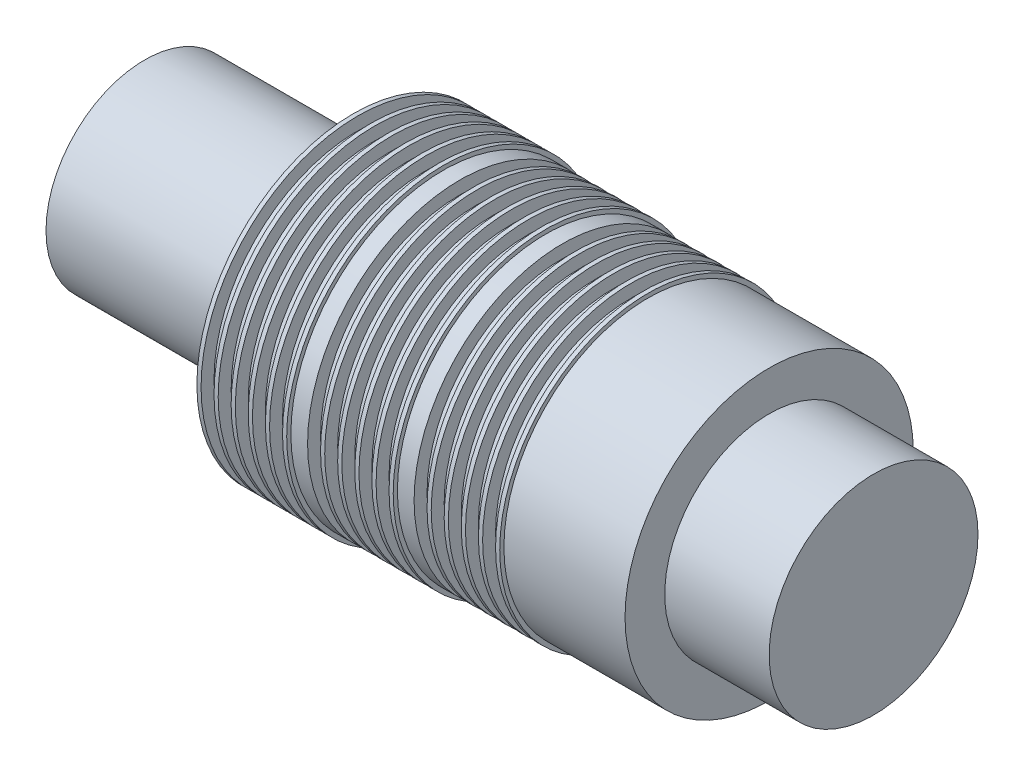
SolidWorks part; units mm, degrees
ref_plane "Front Plane" through (0, 0, 0) normal (0, 0, 1) x (1, 0, 0)
ref_plane "Top Plane" through (0, 0, 0) normal (0, 1, 0) x (1, 0, 0)
ref_plane "Right Plane" through (0, 0, 0) normal (1, 0, 0) x (0, 0, -1)
sketch "Sketch1" plane through (0, 0, 0) normal (0, 0, 1) x (1, 0, 0)
  line L24 (12.954, 9.525) -> (12.954, 8.7376)
  line L25 (12.954, 8.7376) -> (13.7414, 8.7376)
  line L26 (13.7414, 8.7376) -> (13.7414, 9.525)
  line L27 (13.7414, 9.525) -> (13.9954, 9.525)
  line L28 (13.9954, 9.525) -> (13.9954, 8.7376)
  line L29 (13.9954, 8.7376) -> (14.7828, 8.7376)
  line L30 (14.7828, 8.7376) -> (14.7828, 9.525)
  line L31 (14.7828, 9.525) -> (15.0368, 9.525)
  line L32 (15.0368, 9.525) -> (15.0368, 8.7376)
  line L33 (15.0368, 8.7376) -> (15.8242, 8.7376)
  line L34 (15.8242, 8.7376) -> (15.8242, 9.525)
  line L35 (15.8242, 9.525) -> (16.0782, 9.525)
  line L36 (16.0782, 9.525) -> (16.0782, 8.7376)
  line L37 (16.0782, 8.7376) -> (16.8656, 8.7376)
  line L38 (16.8656, 8.7376) -> (16.8656, 9.525)
  line L39 (16.8656, 9.525) -> (17.1196, 9.525)
  line L40 (17.1196, 9.525) -> (17.1196, 8.7376)
  line L41 (17.1196, 8.7376) -> (17.907, 8.7376)
  line L42 (17.907, 8.7376) -> (17.907, 9.525)
  line L43 (17.907, 9.525) -> (18.161, 9.525)
  line L44 (18.161, 9.525) -> (18.161, 9.271)
  line L45 (18.161, 9.271) -> (19.177, 9.271)
  line L46 (19.177, 9.271) -> (19.177, 8.4836)
  line L47 (19.177, 8.4836) -> (19.9644, 8.4836)
  line L48 (19.9644, 8.4836) -> (19.9644, 9.271)
  line L49 (19.9644, 9.271) -> (20.2184, 9.271)
  line L50 (20.2184, 9.271) -> (20.2184, 8.4836)
  line L51 (20.2184, 8.4836) -> (21.0058, 8.4836)
  line L52 (21.0058, 8.4836) -> (21.0058, 9.271)
  line L53 (21.0058, 9.271) -> (21.2598, 9.271)
  line L54 (21.2598, 9.271) -> (21.2598, 8.4836)
  line L55 (21.2598, 8.4836) -> (22.0472, 8.4836)
  line L56 (22.0472, 8.4836) -> (22.0472, 9.271)
  line L57 (22.0472, 9.271) -> (22.3012, 9.271)
  line L58 (22.3012, 9.271) -> (22.3012, 8.4836)
  line L59 (22.3012, 8.4836) -> (23.0886, 8.4836)
  line L60 (23.0886, 8.4836) -> (23.0886, 9.271)
  line L61 (23.0886, 9.271) -> (23.3426, 9.271)
  line L62 (23.3426, 9.271) -> (23.3426, 8.4836)
  line L63 (23.3426, 8.4836) -> (24.13, 8.4836)
  line L64 (24.13, 8.4836) -> (24.13, 9.271)
  line L65 (24.13, 9.271) -> (24.384, 9.271)
  line L66 (24.384, 9.271) -> (24.384, 9.017)
  line L67 (24.384, 9.017) -> (25.4, 9.017)
  line L68 (25.4, 9.017) -> (25.4, 8.2296)
  line L69 (25.4, 8.2296) -> (26.1874, 8.2296)
  line L70 (26.1874, 8.2296) -> (26.1874, 9.017)
  line L71 (26.1874, 9.017) -> (26.4414, 9.017)
  line L72 (26.4414, 9.017) -> (26.4414, 8.2296)
  line L73 (26.4414, 8.2296) -> (27.2288, 8.2296)
  line L74 (27.2288, 8.2296) -> (27.2288, 9.017)
  line L75 (27.2288, 9.017) -> (27.4828, 9.017)
  line L76 (27.4828, 9.017) -> (27.4828, 8.2296)
  line L77 (27.4828, 8.2296) -> (28.2702, 8.2296)
  line L78 (28.2702, 8.2296) -> (28.2702, 9.017)
  line L79 (28.2702, 9.017) -> (28.5242, 9.017)
  line L80 (28.5242, 9.017) -> (28.5242, 8.2296)
  line L81 (28.5242, 8.2296) -> (29.3116, 8.2296)
  line L82 (29.3116, 8.2296) -> (29.3116, 9.017)
  line L83 (29.3116, 9.017) -> (29.5656, 9.017)
  line L84 (29.5656, 9.017) -> (29.5656, 8.2296)
  line L85 (29.5656, 8.2296) -> (30.353, 8.2296)
  line L86 (30.353, 8.2296) -> (30.353, 9.017)
  line L87 (30.353, 9.017) -> (30.607, 9.017)
  line L88 (30.607, 9.017) -> (30.607, 8.763)
  line L89 (30.607, 8.763) -> (31.623, 8.763)
  line L90 (31.623, 8.763) -> (31.623, 7.9756)
  line L91 (31.623, 7.9756) -> (32.4104, 7.9756)
  line L92 (32.4104, 7.9756) -> (32.4104, 8.763)
  line L93 (32.4104, 8.763) -> (32.6644, 8.763)
  line L94 (32.6644, 8.763) -> (32.6644, 7.9756)
  line L95 (32.6644, 7.9756) -> (33.4518, 7.9756)
  line L96 (33.4518, 7.9756) -> (33.4518, 8.763)
  line L97 (33.4518, 8.763) -> (33.7058, 8.763)
  line L98 (33.7058, 8.763) -> (33.7058, 7.9756)
  line L99 (33.7058, 7.9756) -> (34.4932, 7.9756)
  line L100 (34.4932, 7.9756) -> (34.4932, 8.763)
  line L101 (34.4932, 8.763) -> (34.7472, 8.763)
  line L102 (34.7472, 8.763) -> (34.7472, 7.9756)
  line L103 (34.7472, 7.9756) -> (35.5346, 7.9756)
  line L104 (35.5346, 7.9756) -> (35.5346, 8.763)
  line L105 (35.5346, 8.763) -> (35.7886, 8.763)
  line L106 (35.7886, 8.763) -> (35.7886, 7.9756)
  line L107 (35.7886, 7.9756) -> (36.576, 7.9756)
  line L108 (36.576, 7.9756) -> (36.576, 8.763)
  line L109 (36.576, 8.763) -> (36.83, 8.763)
  line L110 (36.83, 8.763) -> (36.83, 8.509)
  line L111 (36.83, 8.509) -> (37.846, 8.509)
  line L112 (37.846, 8.509) -> (37.846, 7.7216)
  line L113 (37.846, 7.7216) -> (38.6334, 7.7216)
  line L114 (38.6334, 7.7216) -> (38.6334, 8.509)
  line L115 (38.6334, 8.509) -> (38.8874, 8.509)
  line L116 (38.8874, 8.509) -> (38.8874, 7.7216)
  line L117 (38.8874, 7.7216) -> (39.6748, 7.7216)
  line L118 (39.6748, 7.7216) -> (39.6748, 8.509)
  line L119 (39.6748, 8.509) -> (39.9288, 8.509)
  line L120 (39.9288, 8.509) -> (39.9288, 7.7216)
  line L121 (39.9288, 7.7216) -> (40.7162, 7.7216)
  line L122 (40.7162, 7.7216) -> (40.7162, 8.509)
  line L123 (40.7162, 8.509) -> (40.9702, 8.509)
  line L124 (40.9702, 8.509) -> (40.9702, 7.7216)
  line L125 (40.9702, 7.7216) -> (41.7576, 7.7216)
  line L126 (41.7576, 7.7216) -> (41.7576, 8.509)
  line L127 (41.7576, 8.509) -> (42.0116, 8.509)
  line L128 (42.0116, 8.509) -> (42.0116, 7.7216)
  line L129 (42.0116, 7.7216) -> (42.799, 7.7216)
  line L130 (42.799, 7.7216) -> (42.799, 8.509)
  line L131 (42.799, 8.509) -> (43.053, 8.509)
  line L132 (43.053, 8.509) -> (43.053, 8.255)
  line L133 (43.053, 8.255) -> (44.069, 8.255)
  line L134 (44.069, 8.255) -> (44.069, 7.4676)
  line L135 (44.069, 7.4676) -> (44.8564, 7.4676)
  line L136 (44.8564, 7.4676) -> (44.8564, 8.255)
  line L137 (44.8564, 8.255) -> (45.1104, 8.255)
  line L138 (45.1104, 8.255) -> (45.1104, 7.4676)
  line L139 (45.1104, 7.4676) -> (45.8978, 7.4676)
  line L140 (45.8978, 7.4676) -> (45.8978, 8.255)
  line L141 (45.8978, 8.255) -> (46.1518, 8.255)
  line L142 (46.1518, 8.255) -> (46.1518, 7.4676)
  line L143 (46.1518, 7.4676) -> (46.9392, 7.4676)
  line L144 (46.9392, 7.4676) -> (46.9392, 8.255)
  line L145 (46.9392, 8.255) -> (47.1932, 8.255)
  line L146 (47.1932, 8.255) -> (47.1932, 7.4676)
  line L147 (47.1932, 7.4676) -> (47.9806, 7.4676)
  line L148 (47.9806, 7.4676) -> (47.9806, 8.255)
  line L149 (47.9806, 8.255) -> (48.2346, 8.255)
  line L150 (48.2346, 8.255) -> (48.2346, 7.4676)
  line L151 (48.2346, 7.4676) -> (49.022, 7.4676)
  line L152 (49.022, 7.4676) -> (49.022, 8.255)
  line L153 (49.022, 8.255) -> (49.276, 8.255)
  line L156 (12.7, 6) -> (0, 6)
  line L157 (0, 6) -> (0, 0)
  line L158 (0, 0) -> (61.976, 0)
  line L160 (12.954, 9.525) -> (12.7, 9.525)
  line L161 (12.7, 9.525) -> (12.7, 6)
  line L162 (49.276, 6) -> (69.596, 6)
  line L163 (69.596, 6) -> (69.596, 0)
  line L164 (69.596, 0) -> (61.976, 0)
  line L165 (49.276, 8.255) -> (49.276, 6)
  point P5 (12.827, 9.525)
  point P6 (59.436, 6)
  dimension "D1" = 6
  dimension "D9" = 12.7
  dimension "D3" = 0.254
  dimension "D4" = 0.7874
  dimension "D5" = 0.7874
  dimension "D7" = 1.016
  dimension "D10" = 6
  dimension "D11" = 20.32
  dimension "D2" = 9.525
  dimension "D6" = 0.254
revolve "Revolve1" add sketch "Sketch1" angle 360 about L158
ref_plane "split plane" through (31.623, 0, 0) normal (1, 0, 0) x (0, 0, -1)
sketch "Sketch3" plane through (31.623, 0, 0) normal (1, 0, 0) x (0, 0, -1)
  circle A0 centre (0, 0) radius 17.3578
extrude "Cut-Extrude1" cut sketch "Sketch3" along normal blind 114.5794
sketch "Sketch4" plane through (31.623, 0, 0) normal (1, 0, 0) x (0, 0, -1)
  circle A0 centre (0, 0) radius 6.35
  dimension "D1" = 12.7
extrude "Boss-Extrude1" add sketch "Sketch4" along normal blind 12.7
sketch "Sketch5" plane through (31.623, 0, 0) normal (1, 0, 0) x (0, 0, -1)
  circle A0 centre (0, 0) radius 8.763
  circle A1 centre (0, 0) radius 6.35 construction
  circle A2 centre (0, 0) radius 6.35
extrude "Boss-Extrude2" add sketch "Sketch5" along normal blind 6.35
sketch "Sketch6" plane through (37.973, 0, 0) normal (1, 0, 0) x (0, 0, -1)
  circle A0 centre (0, 0) radius 7.6624
equation "\"kero_radius\"=0.23622in"
equation "\"D1@Sketch1\"=\"kero_radius\""
equation "\"lox_radius\"=0.23622in"
equation "\"Cavity_width\"=0.031in"
equation "\"tooth_width\"=0.01in"
equation "\"cavity_depth\"=0.031in"
equation "\"seal_step\"=0.01in"
equation "\"purge_length\"=0.04in"
equation "\"D3@Sketch1\"=\"tooth_width\""
equation "\"D4@Sketch1\"=\"Cavity_width\""
equation "\"D5@Sketch1\"=\"cavity_depth\""
equation "\"D7@Sketch1\"=\"purge_length\""
equation "\"D10@Sketch1\"=\"lox_radius\""
equation "\"lox_in_radius\"=.375in"
equation "\"bearing_radius\"= 0.629921"
equation "\"bearing_width\"=0.393701"
equation "\"insert_radius\" = 0.5925in"
equation "\"recycle_groove width\" = 0.05in"
equation "\"recycle_groove_depth\" = 0.04in"
equation "\"N2_purge_width\"= .05in"
equation "\"N2_purge_depth\"= .04in"
equation "\"drain_width\"= .05in"
equation "\"drain_depth\"= .04in"
equation "\"radial_clearance\"= .002in"
equation "\"IPS_flange_width\"= .25in"
equation "\"IPS_flange_radius\" = 2.2in"
equation "\"IPS_LOX_male_radius\"= .9in"
equation "\"IPS_Kero_male_radius\" = .9in"
equation "\"IPS_radius\"= 1.4in"
equation "\"InsertLength\"= 1.445in"
equation "\"D2@Sketch1\"=\"lox_in_radius\""
equation "\"D6@Sketch1\"=\"seal_step\""
